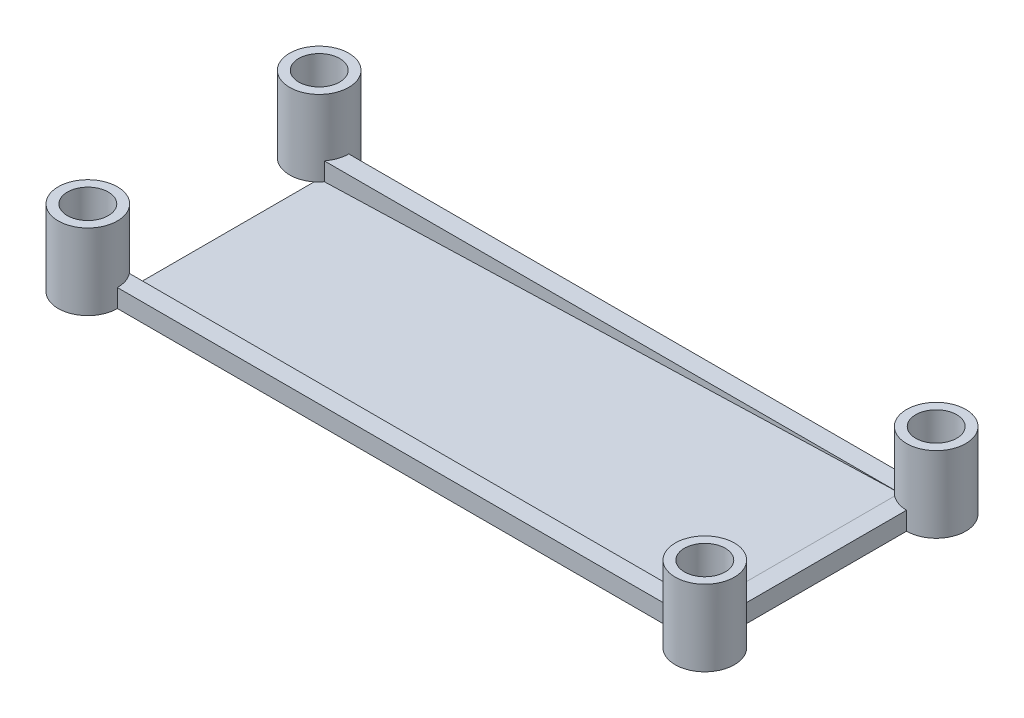
SolidWorks part; units mm, degrees
ref_plane "Front Plane" through (0, 0, 0) normal (0, 0, 1) x (1, 0, 0)
ref_plane "Top Plane" through (0, 0, 0) normal (0, 1, 0) x (1, 0, 0)
ref_plane "Right Plane" through (0, 0, 0) normal (1, 0, 0) x (0, 0, -1)
sketch "Sketch1" plane through (0, 0, 0) normal (0, 1, 0) x (1, 0, 0)
  line L1 (-203.2, -76.2) -> (203.2, -76.2)
  line L2 (-203.2, -76.2) -> (-203.2, 76.2)
  line L3 (-203.2, 76.2) -> (203.2, 76.2)
  line L4 (203.2, -76.2) -> (203.2, 76.2)
  line L5 (-203.2, -76.2) -> (203.2, 76.2) construction
  line L6 (-203.2, 76.2) -> (203.2, -76.2) construction
  point P1 (0, 0)
  dimension "D1" = 406.4
  dimension "D2" = 152.4
extrude "Boss-Extrude1" add sketch "Sketch1" along normal blind 12
sketch "Sketch2" plane through (0, 12, 0) normal (0, 1, 0) x (1, 0, 0)
  line L0 (-203.2, -64.2) -> (-191.2, -64.2)
  line L10 (-191.2, 64.2) -> (-203.2, 64.2)
  line L11 (-203.2, 76.2) -> (-203.2, -76.2) construction
  line L12 (-203.2, 64.2) -> (-203.2, -64.2)
  line L14 (191.2, -64.2) -> (191.2, 64.2)
  line L15 (-191.2, -64.2) -> (191.2, -64.2)
  line L16 (-191.2, 64.2) -> (-191.2, -64.2)
  line L17 (191.2, 64.2) -> (-191.2, 64.2)
  line L18 (191.2, -64.2) -> (191.2, 64.2)
  line L19 (-191.2, -64.2) -> (191.2, -64.2)
  line L21 (191.2, 64.2) -> (-191.2, 64.2)
  dimension "D1" = 12
extrude "Cut-Extrude1" cut sketch "Sketch2" against normal blind 12
sketch "Sketch3" plane through (0, 0, -64.2) normal (0, 0, 1) x (1, 0, 0)
  line L2 (-191.2, 12) -> (-191.2, 0)
  line L3 (-191.2, 12) -> (-191.2, 0) construction
  line L4 (-191.2, 0) -> (191.2, 12)
  line L5 (191.2, 12) -> (191.2, 0)
  line L6 (191.2, 12) -> (191.2, 0) construction
  line L7 (191.2, 12) -> (191.2, 0)
  line L8 (191.2, 0) -> (-191.2, 0)
  dimension "D1" = 12
  dimension "D2" = 12
extrude "Boss-Extrude2" add sketch "Sketch3" along normal up to next
sketch "Sketch4" plane through (0, 0, 0) normal (0, 1, 0) x (1, 0, 0)
  circle A1 centre (-203.2, -76.2) radius 13.4938
  circle A2 centre (-203.2, -76.2) radius 19.4938
  dimension "D1" = 26.9875
  dimension "D2" = 6
extrude "Boss-Extrude3" add sketch "Sketch4" along normal blind 50
extrude "Cut-Extrude2" cut sketch "Sketch4<2>" along normal blind 50 contours A1
sketch "Sketch4<2>" plane through (0, 0, 0) normal (0, 1, 0) x (1, 0, 0) same geometry as "Sketch4"
extrude "Boss-Extrude4" add sketch "Sketch4<3>" along normal blind 12 contours A1
sketch "Sketch4<3>" plane through (0, 0, 0) normal (0, 1, 0) x (1, 0, 0) same geometry as "Sketch4"
mirror "Mirror1" about plane through (0, 0, 0) normal (1, 0, 0) of "Boss-Extrude4", "Cut-Extrude2", "Boss-Extrude3" second plane through (0, 0, 0) second plane normal (0, 0, 1)
